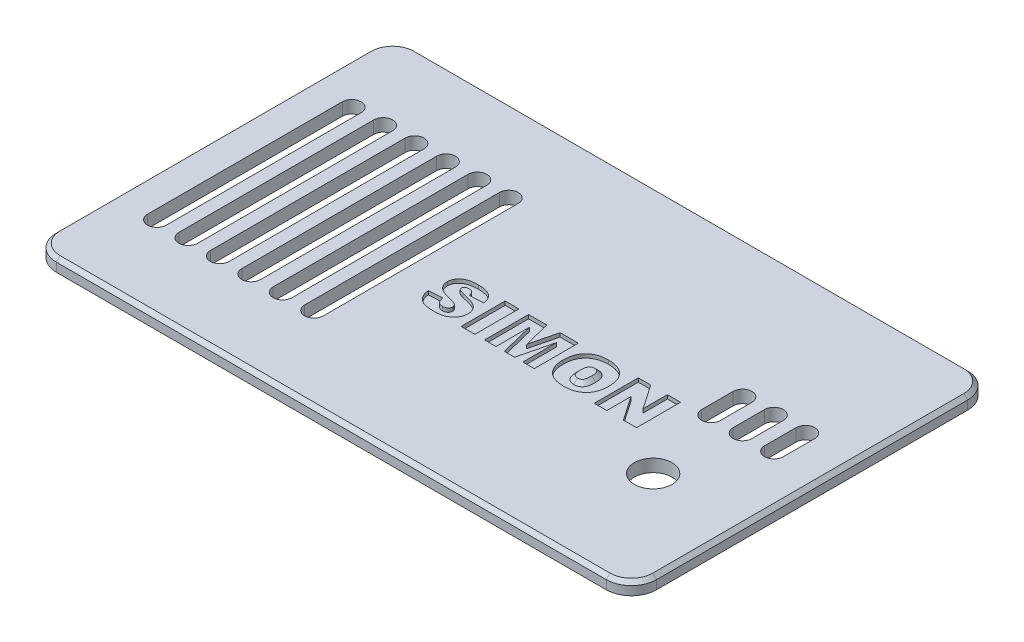
SolidWorks part; units mm, degrees
ref_plane "Front Plane" through (0, 0, 0) normal (0, 0, 1) x (1, 0, 0)
ref_plane "Top Plane" through (0, 0, 0) normal (0, 1, 0) x (1, 0, 0)
ref_plane "Right Plane" through (0, 0, 0) normal (1, 0, 0) x (0, 0, -1)
sketch "Croquis_tapa" plane through (0, 0, 0) normal (0, 1, 0) x (1, 0, 0)
  line L0 (-43.75, -28.75) -> (43.75, -28.75)
  line L1 (47.75, -24.75) -> (47.75, 24.75)
  line L2 (43.75, 28.75) -> (-43.75, 28.75)
  line L3 (-47.75, 24.75) -> (-47.75, -24.75)
  arc A0 (43.75, -28.75) -> (47.75, -24.75) centre (43.75, -24.75) ccw
  arc A1 (47.75, 24.75) -> (43.75, 28.75) centre (43.75, 24.75) ccw
  arc A2 (-43.75, 28.75) -> (-47.75, 24.75) centre (-43.75, 24.75) ccw
  arc A3 (-47.75, -24.75) -> (-43.75, -28.75) centre (-43.75, -24.75) ccw
  dimension "D3" = 4
  dimension "D1" = 95.5
  dimension "D2" = 57.5
extrude "Tapa" add sketch "Croquis_tapa" along normal blind 2
sketch "Croquis_ventana_y_ventilas" plane through (0, 0, 0) normal (0, 1, 0) x (1, 0, 0)
  line L0 (-16, -15.5) -> (-16, 15.5) construction
  line L1 (-17.5, -15.5) -> (-17.5, 15.5)
  line L2 (-14.5, -15.5) -> (-14.5, 15.5)
  line L3 (-21, -15.5) -> (-21, 15.5) construction
  line L4 (-22.5, -15.5) -> (-22.5, 15.5)
  line L5 (-19.5, -15.5) -> (-19.5, 15.5)
  line L6 (-26, -15.5) -> (-26, 15.5) construction
  line L7 (-27.5, -15.5) -> (-27.5, 15.5)
  line L8 (-24.5, -15.5) -> (-24.5, 15.5)
  line L9 (-31, -15.5) -> (-31, 15.5) construction
  line L10 (-32.5, -15.5) -> (-32.5, 15.5)
  line L11 (-29.5, -15.5) -> (-29.5, 15.5)
  line L12 (-36, -15.5) -> (-36, 15.5) construction
  line L13 (-37.5, -15.5) -> (-37.5, 15.5)
  line L14 (-34.5, -15.5) -> (-34.5, 15.5)
  line L15 (-41, -15.5) -> (-41, 15.5) construction
  line L16 (-42.5, -15.5) -> (-42.5, 15.5)
  line L17 (-39.5, -15.5) -> (-39.5, 15.5)
  line L18 (30, 1.68) -> (30, 6.68) construction
  line L19 (28.5, 1.68) -> (28.5, 6.68)
  line L20 (31.5, 1.68) -> (31.5, 6.68)
  line L21 (35, 1.68) -> (35, 6.68) construction
  line L22 (33.5, 1.68) -> (33.5, 6.68)
  line L23 (36.5, 1.68) -> (36.5, 6.68)
  line L24 (40, 1.68) -> (40, 6.68) construction
  line L25 (38.5, 1.68) -> (38.5, 6.68)
  line L26 (41.5, 1.68) -> (41.5, 6.68)
  circle A0 centre (33.46, -11) radius 3
  arc A1 (-17.5, -15.5) -> (-14.5, -15.5) centre (-16, -15.5) ccw
  arc A2 (-14.5, 15.5) -> (-17.5, 15.5) centre (-16, 15.5) ccw
  arc A3 (-22.5, -15.5) -> (-19.5, -15.5) centre (-21, -15.5) ccw
  arc A4 (-19.5, 15.5) -> (-22.5, 15.5) centre (-21, 15.5) ccw
  arc A5 (-27.5, -15.5) -> (-24.5, -15.5) centre (-26, -15.5) ccw
  arc A6 (-24.5, 15.5) -> (-27.5, 15.5) centre (-26, 15.5) ccw
  arc A7 (-32.5, -15.5) -> (-29.5, -15.5) centre (-31, -15.5) ccw
  arc A8 (-29.5, 15.5) -> (-32.5, 15.5) centre (-31, 15.5) ccw
  arc A9 (-37.5, -15.5) -> (-34.5, -15.5) centre (-36, -15.5) ccw
  arc A10 (-34.5, 15.5) -> (-37.5, 15.5) centre (-36, 15.5) ccw
  arc A11 (-42.5, -15.5) -> (-39.5, -15.5) centre (-41, -15.5) ccw
  arc A12 (-39.5, 15.5) -> (-42.5, 15.5) centre (-41, 15.5) ccw
  arc A13 (28.5, 1.68) -> (31.5, 1.68) centre (30, 1.68) ccw
  arc A14 (31.5, 6.68) -> (28.5, 6.68) centre (30, 6.68) ccw
  arc A15 (33.5, 1.68) -> (36.5, 1.68) centre (35, 1.68) ccw
  arc A16 (36.5, 6.68) -> (33.5, 6.68) centre (35, 6.68) ccw
  arc A17 (38.5, 1.68) -> (41.5, 1.68) centre (40, 1.68) ccw
  arc A18 (41.5, 6.68) -> (38.5, 6.68) centre (40, 6.68) ccw
  point P4 (-16, 0)
  point P9 (-21, 0)
  point P16 (-26, 0)
  point P23 (-31, 0)
  point P30 (-36, 0)
  point P37 (-41, 0)
  point P44 (30, 4.18)
  point P51 (35, 4.18)
  point P58 (40, 4.18)
  point P65 (0, 0)
  dimension "D1" = 6
extrude "Ventana_LDR_y_ventilas" cut sketch "Croquis_ventana_y_ventilas" along normal through all and the other way through all
ref_plane "Plano_Top Plane_+2" through (0, 2, 0) normal (0, 1, 0) x (1, 0, 0)
sketch "Croquis_texto" plane through (0, 2, 0) normal (0, 1, 0) x (1, 0, 0)
  text T0 "SIMON" font "Arial Black" height 7
extrude "Texto_SIMON" cut sketch "Croquis_texto" against normal blind 0.6
chamfer "Chaflan_cara_superior" distance 0.6 angle 45 12 edges at (-47.75, 2, 0) (-46.5784, 2, -27.5784) (0, 2, -28.75) (46.5784, 2, -27.5784) (47.75, 2, 0) (46.5784, 2, 27.5784) (0, 2, 28.75) (-46.5784, 2, 27.5784) tangent propagation no
